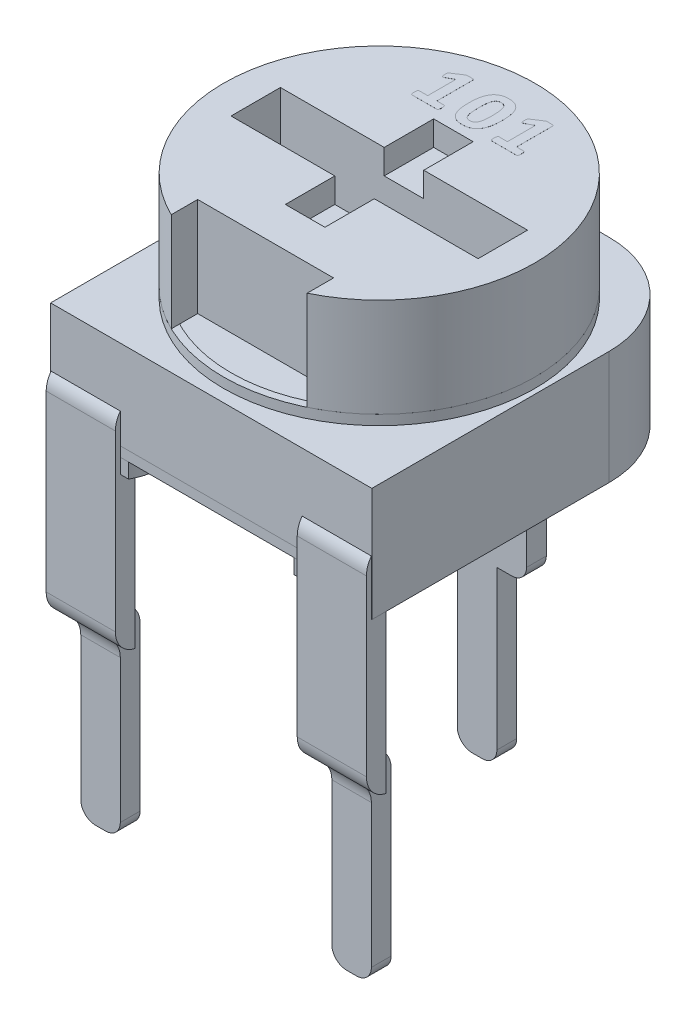
SolidWorks part; units mm, degrees
material "ABS"
ref_plane "Front Plane" through (0, 0, 0) normal (0, 0, 1) x (1, 0, 0)
ref_plane "Top Plane" through (0, 0, 0) normal (0, 1, 0) x (1, 0, 0)
ref_plane "Right Plane" through (0, 0, 0) normal (1, 0, 0) x (0, 0, -1)
sketch "Sketch1" plane through (0, 0, 0) normal (0, 1, 0) x (1, 0, 0)
  line L0 (0, 3.15) -> (0, -3.15) construction
  line L1 (0, 3.15) -> (0, 3.4) construction
  line L2 (0, -3.15) -> (0, -3.4) construction
  line L3 (-3.15, 0) -> (3.15, 0) construction
  line L4 (3.15, 0) -> (3.25, 0) construction
  line L5 (-3.15, 0) -> (-3.25, 0) construction
  line L6 (-3.25, -3.4) -> (3.25, -3.4)
  line L7 (-3.25, -3.4) -> (-3.25, 3.4)
  line L8 (-3.25, 3.4) -> (3.25, 3.4)
  line L9 (3.25, 3.4) -> (3.25, -3.4)
  circle A0 centre (0, 0) radius 3.15 construction
  dimension "D1" = 6.3
  dimension "D2" = 6.8
  dimension "D3" = 6.5
extrude "Boss-Extrude1" add sketch "Sketch1" along normal blind 2.3
sketch "Sketch2" plane through (0, 2.3, 0) normal (0, 1, 0) x (1, 0, 0)
  circle A0 centre (0, 0) radius 3.15 construction
  circle A1 centre (0, 0) radius 3.15
extrude "Boss-Extrude2" add sketch "Sketch2" along normal blind 0.2
fillet "Fillet1" radius 2 2 edges at (3.25, 1.15, -3.4) (-3.25, 1.15, -3.4)
sketch "Sketch3" plane through (0, 0, 0) normal (0, -1, 0) x (1, 0, 0)
  line L0 (0, 0) -> (0, -2.5) construction
  line L1 (-1.75, -2.5) -> (1.75, -2.5)
  line L6 (-2.25, -2) -> (-2.25, 2)
  line L7 (2.25, -2) -> (2.25, 2)
  line L8 (-2.25, 2) -> (-3, 2)
  line L9 (-3, 2) -> (-3, 3.4)
  line L10 (-3.25, 3.4) -> (3.25, 3.4) construction
  line L11 (2.25, 2) -> (3, 2)
  line L12 (3, 2) -> (3, 3.4)
  line L13 (3, 3.4) -> (-3, 3.4)
  line L14 (0, 0) -> (0, 3.4) construction
  arc A0 (-1.75, -2.5) -> (-2.25, -2) centre (-1.75, -2) cw
  arc A1 (1.75, -2.5) -> (2.25, -2) centre (1.75, -2) ccw
  point P20 (2.25, -2.5)
  dimension "D6" = 0.5
  dimension "D1" = 4.5
  dimension "D2" = 2.5
  dimension "D3" = 4.5
  dimension "D4" = 1.4
  dimension "D5" = 6
extrude "Cut-Extrude1" cut sketch "Sketch3" against normal blind 0.5
sketch "Sketch4" plane through (0, 0.5, 0) normal (0, -1, 0) x (1, 0, 0)
  line L8 (-3, 2) -> (-2.25, 2)
  line L9 (-2.25, 2) -> (-2.25, -2)
  line L10 (-1.75, -2.5) -> (1.75, -2.5)
  line L11 (2.25, -2) -> (2.25, 2)
  line L12 (2.25, 2) -> (3, 2)
  line L13 (3, 2) -> (3, 3.4)
  line L14 (3, 3.4) -> (-3, 3.4)
  line L15 (-3, 3.4) -> (-3, 2)
  line L16 (-3, 2) -> (-2.25, 2)
  line L17 (-2.25, 2) -> (-2.25, -2)
  line L18 (-1.75, -2.5) -> (1.75, -2.5)
  line L19 (2.25, -2) -> (2.25, 2)
  line L20 (2.25, 2) -> (3, 2)
  line L21 (3, 2) -> (3, 3.4)
  line L22 (3, 3.4) -> (-3, 3.4)
  line L23 (-3, 3.4) -> (-3, 2)
  arc A2 (-2.25, -2) -> (-1.75, -2.5) centre (-1.75, -2) ccw
  arc A3 (1.75, -2.5) -> (2.25, -2) centre (1.75, -2) ccw
  arc A4 (-2.25, -2) -> (-1.75, -2.5) centre (-1.75, -2) ccw
  arc A5 (1.75, -2.5) -> (2.25, -2) centre (1.75, -2) ccw
  dimension "D1" = 0
extrude "Boss-Extrude3" add sketch "Sketch4" along normal blind 0.2 separate body
sketch "Sketch5" plane through (0, 0.3, 0) normal (0, -1, 0) x (1, 0, 0)
  line L0 (0, 3.4) -> (0, 2.9) construction
  line L1 (3, 3.4) -> (-3, 3.4) construction
  line L2 (0, 2.9) -> (0, -2.18) construction
  line L3 (-2.54, 2.9) -> (2.54, 2.9) construction
  circle A0 centre (2.54, 2.9) radius 1
  circle A1 centre (-2.54, 2.9) radius 1
  circle A2 centre (0, -2.18) radius 1
  dimension "D2" = 5.08
  dimension "D4" = 2
  dimension "D1" = 0.5
  dimension "D3" = 5.08
extrude "Boss-Extrude4" add sketch "Sketch5" along normal up to surface (0.3 mm away) up to face at (0, 0, 0.1228)
sketch "Sketch6" plane through (0, 0.3, 0) normal (0, 1, 0) x (1, 0, 0)
  line L0 (-3.25, -3.4) -> (-3.25, -1)
  line L1 (-3.25, 1.4) -> (-3.25, -3.4) construction
  line L2 (-3.25, -1) -> (-4.35, -1)
  line L3 (-4.35, -1) -> (-4.35, -4.5)
  line L4 (-4.35, -4.5) -> (4.35, -4.5)
  line L5 (4.35, -4.5) -> (4.35, -1)
  line L6 (4.35, -1) -> (3.25, -1)
  line L7 (3.25, -3.4) -> (3.25, 1.4) construction
  line L8 (-3.25, -3.4) -> (3.25, -3.4)
  line L9 (3.25, -3.4) -> (3.25, -1)
  line L10 (0, 0) -> (0, -3.4) construction
  line L11 (0, -3.4) -> (0, -4.5) construction
  dimension "D1" = 3.5
extrude "Cut-Extrude2" cut sketch "Sketch6" against normal up to surface (0.3 mm away) up to face at (0, 0, -0.817)
sketch "Sketch8" plane through (0, 0.3, 0) normal (0, -1, 0) x (1, 0, 0)
  line L1 (-0.4, -1.98) -> (0.4, -1.98)
  line L2 (-0.4, -1.98) -> (-0.4, -2.38)
  line L3 (-0.4, -2.38) -> (0.4, -2.38)
  line L4 (0.4, -1.98) -> (0.4, -2.38)
  line L5 (-0.4, -1.98) -> (0.4, -2.38) construction
  line L6 (-0.4, -2.38) -> (0.4, -1.98) construction
  line L7 (-2.94, 3.1) -> (-2.14, 3.1)
  line L8 (-2.94, 3.1) -> (-2.94, 2.7)
  line L9 (-2.94, 2.7) -> (-2.14, 2.7)
  line L10 (-2.14, 3.1) -> (-2.14, 2.7)
  line L11 (-2.94, 3.1) -> (-2.14, 2.7) construction
  line L12 (-2.94, 2.7) -> (-2.14, 3.1) construction
  line L13 (2.94, 3.1) -> (2.14, 3.1)
  line L14 (2.94, 3.1) -> (2.94, 2.7)
  line L15 (2.94, 2.7) -> (2.14, 2.7)
  line L16 (2.14, 3.1) -> (2.14, 2.7)
  line L17 (2.94, 3.1) -> (2.14, 2.7) construction
  line L18 (2.94, 2.7) -> (2.14, 3.1) construction
  point P0 (0, -2.18)
  point P5 (-2.54, 2.9)
  point P11 (2.54, 2.9)
  dimension "D1" = 0.4
  dimension "D2" = 0.8
extrude "Boss-Extrude5" add sketch "Sketch8" along normal blind 7
sketch "Sketch9" plane through (0, 0.3, 0) normal (0, -1, 0) x (1, 0, 0)
  line L4 (0, -1.98) -> (0, -2.38) construction
  line L5 (0.4, -1.98) -> (-0.4, -1.98) construction
  line L6 (-0.4, -2.38) -> (0.4, -2.38) construction
  line L8 (-1, -1.98) -> (1, -1.98)
  line L9 (-1, -1.98) -> (-1, -2.38)
  line L10 (-1, -2.38) -> (1, -2.38)
  line L11 (1, -1.98) -> (1, -2.38)
  line L12 (-1, -1.98) -> (1, -2.38) construction
  line L13 (-1, -2.38) -> (1, -1.98) construction
  point P14 (0, -2.18)
  dimension "D1" = 2
extrude "Boss-Extrude6" add sketch "Sketch9" along normal blind 3.5
sketch "Sketch10" plane through (0, 0.3, 0) normal (0, -1, 0) x (1, 0, 0)
  line L0 (-2.54, 3.1) -> (-2.54, 3.5) construction
  line L1 (-2.14, 3.1) -> (-2.94, 3.1) construction
  line L2 (2.54, 3.1) -> (2.54, 3.5) construction
  line L3 (2.94, 3.1) -> (2.14, 3.1) construction
  line L4 (-2.94, 3.1) -> (-2.94, 2.7) construction
  line L5 (-3.24, 3.5) -> (-1.84, 3.5)
  line L6 (-3.24, 3.5) -> (-3.24, 3.1)
  line L7 (-3.24, 3.1) -> (-1.84, 3.1)
  line L8 (-1.84, 3.5) -> (-1.84, 3.1)
  line L10 (1.84, 3.5) -> (3.24, 3.5)
  line L11 (1.84, 3.5) -> (1.84, 3.1)
  line L12 (1.84, 3.1) -> (3.24, 3.1)
  line L13 (3.24, 3.5) -> (3.24, 3.1)
  dimension "D1" = 1.4
extrude "Boss-Extrude7" add sketch "Sketch10" along normal blind 3.5 and the other way blind 1
fillet "Fillet2" radius 0.5 2 edges at (2.54, 1.3, 3.5) (-2.54, 1.3, 3.5)
sketch "Sketch11" plane through (0, 0, 0) normal (1, 0, 0) x (0, 0, -1)
  line L0 (-3.4, 0) -> (1.4, 0) construction
  line L1 (-3.1, -2.8) -> (-2.7, -2.8)
  line L2 (-3.1, -2.8) -> (-3.1, 0)
  line L3 (-3.1, 0) -> (-2.7, 0)
  line L4 (-2.7, -2.8) -> (-2.7, 0)
  line L5 (-2.7, -6.7) -> (-2.7, 0.3) construction
  line L6 (-3.1, -2.8) -> (-3.1, -3.2) construction
extrude "Cut-Extrude3" cut sketch "Sketch11" against normal through all both and the other way through all
fillet "Fillet3" radius 0.5 4 edges at (-2.54, -2.8, 3.1) (2.54, -2.8, 3.1) (-2.54, -3.2, 3.5) (2.54, -3.2, 3.5)
fillet "Fillet4" radius 0.5 4 edges at (2.54, -2.8, 2.7) (-2.54, -2.8, 2.7) (2.54, -3.2, 3.1) (-2.54, -3.2, 3.1)
fillet "Fillet5" radius 0.3 12 edges at (-1, -3.2, -2.18) (1, -3.2, -2.18) (-0.4, -6.7, -2.18) (0.4, -6.7, -2.18) (2.14, -6.7, 2.9) (2.94, -6.7, 2.9) (-2.94, -6.7, 2.9) (-2.14, -6.7, 2.9) (-2.14, -2.7551, 3.1) (-2.94, -2.7551, 3.1) (2.14, -2.7551, 3.1) (2.94, -2.7551, 3.1)
sketch "Sketch12" plane through (0, 0.3, 0) normal (0, -1, 0) x (1, 0, 0)
  circle A0 centre (0, 0) radius 2
  circle A1 centre (0, 0) radius 1.5
  dimension "D1" = 4
  dimension "D2" = 3
extrude "Boss-Extrude8" add sketch "Sketch12" along normal blind 0.15
sketch "Sketch15" plane through (0, 2.5, 0) normal (0, 1, 0) x (1, 0, 0)
  circle A0 centre (0, 0) radius 3
  dimension "D1" = 6
extrude "Cut-Extrude4" cut sketch "Sketch15" against normal blind 0.5
sketch "Sketch14" plane through (0, 2.5, 0) normal (0, 1, 0) x (1, 0, 0)
  circle A1 centre (0, 0) radius 3.15
  circle A2 centre (0, 0) radius 3.15
  dimension "D1" = 0
extrude "Boss-Extrude9" add sketch "Sketch14" along normal blind 2 separate body
sketch "Set Angle of Knob" plane through (0, 4.5, 0) normal (0, 1, 0) x (1, 0, 0)
  line L0 (0, 0) -> (0, -3.15) construction
  line L1 (-2.5, 0) -> (2.5, 0) construction
  line L2 (-2.5, 0.5) -> (-2.5, -0.5)
  line L3 (2.5, 0.5) -> (2.5, -0.5)
  line L4 (-2.5, 0.5) -> (-0.4, 0.5)
  line L5 (-2.5, -0.5) -> (-0.4, -0.5)
  line L6 (0, 0) -> (0, -1.5) construction
  line L7 (0, 0) -> (0, 1.5) construction
  line L8 (0, 1.5) -> (0, 3.15) construction
  line L9 (0.4, 1.5) -> (-0.4, 1.5)
  line L10 (0.4, 1.5) -> (0.4, 0.5)
  line L11 (-0.4, 1.5) -> (-0.4, 0.5)
  line L12 (0.4, 0.5) -> (2.5, 0.5)
  line L13 (-0.4, -1.5) -> (0.4, -1.5)
  line L14 (-0.4, -1.5) -> (-0.4, -0.5)
  line L15 (0.4, -1.5) -> (0.4, -0.5)
  line L16 (0.4, -0.5) -> (2.5, -0.5)
  line L17 (0, -1.5) -> (0, -2.3) construction
  line L18 (-1.375, -2.3) -> (1.375, -2.3)
  line L19 (-1.375, -2.3) -> (-1.375, -3.8)
  line L20 (1.375, -2.3) -> (1.375, -3.8)
  line L21 (-1.375, -3.8) -> (1.375, -3.8)
  line L22 (-1, 0.25) -> (1, 0.25) construction
  line L23 (-1, 0.25) -> (-1, -0.25) construction
  line L24 (-1, -0.25) -> (1, -0.25) construction
  line L25 (1, -0.25) -> (1, 0.25) construction
  circle A0 centre (0, 0) radius 3.15 construction
  circle A1 centre (0, 0) radius 3.15 construction
  point P32 (0, 0.25)
  dimension "D1" = 1
  dimension "D2" = 0.8
  dimension "D3" = 1.5
  dimension "D4" = 5
  dimension "D5" = 90
  dimension "D6" = 2.75
  dimension "D7" = 1.5
  dimension "D8" = 1.8
  dimension "D9" = 0.25
  dimension "D10" = 0.25
  dimension "D11" = 2
extrude "TURN KNOB" cut sketch "Set Angle of Knob" against normal blind 2.3
sketch "Sketch17" plane through (0, 2, 0) normal (0, 1, 0) x (1, 0, 0)
  line L0 (-0.4, -1.5) -> (0.4, -1.5)
  line L1 (0.4, -1.5) -> (0.4, -0.5)
  line L2 (0.4, 1.5) -> (-0.4, 1.5)
  line L3 (-0.4, 1.5) -> (-0.4, 0.5)
  line L4 (-0.4, 0.5) -> (0.4, 0.5)
  line L5 (-0.4, -0.5) -> (0.4, -0.5)
  line L6 (-0.4, -0.5) -> (-0.4, -1.5)
  line L7 (0.4, 0.5) -> (0.4, 1.5)
extrude "Boss-Extrude10" add sketch "Sketch17" along normal blind 2
sketch "Sketch20" plane through (0, 2, 0) normal (0, 1, 0) x (1, 0, 0)
  line L0 (-1, 0.25) -> (1, 0.25) construction
  line L1 (-1, 0.25) -> (1, 0.25)
  line L2 (-1, -0.25) -> (1, -0.25) construction
  line L3 (-1, -0.25) -> (1, -0.25)
  line L4 (-1, 0.25) -> (-1, -0.25) construction
  line L5 (-1, 0.25) -> (-1, -0.25)
  line L6 (1, -0.25) -> (1, 0.25) construction
  line L7 (1, -0.25) -> (1, 0.25)
extrude "Cut-Extrude6" cut sketch "Sketch20" against normal blind 0.5
fillet "Fillet6" radius 0.2 2 edges at (1, 2, 0) (-1, 2, 0)
sketch "See Code in Properties" plane through (0, 4.5, 0) normal (0, 1, 0) x (1, 0, 0)
  line L0 (0, 1.5) -> (0, 1.7) construction
  line L1 (0.4, 1.5) -> (-0.4, 1.5) construction
  line L2 (0, 1.5) -> (0, 3.15) construction
  line L3 (-1.5, 1.7) -> (1.5, 1.7) construction
  text T0 "101" font "Calibri" height 0.9
  dimension "D1" = 0.2
  dimension "D2" = 3
extrude "Code Number" add sketch "See Code in Properties" along normal blind 0.001
